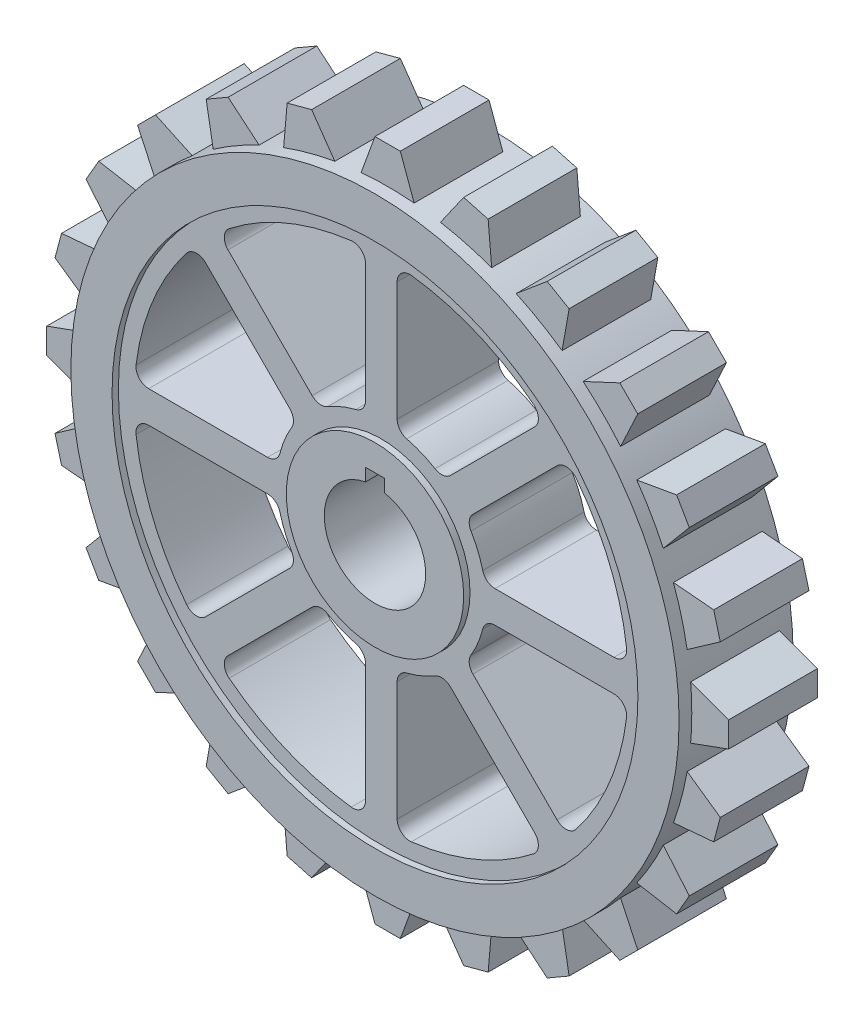
SolidWorks part; units mm, degrees
ref_plane "Front Plane" through (0, 0, 0) normal (0, 0, 1) x (1, 0, 0)
ref_plane "Top Plane" through (0, 0, 0) normal (0, 1, 0) x (1, 0, 0)
ref_plane "Right Plane" through (0, 0, 0) normal (1, 0, 0) x (0, 0, -1)
sketch "Sketch1" plane through (0, 0, 0) normal (0, 0, 1) x (1, 0, 0)
  line L0 (0, 54.6854) -> (0, -14) construction
  line L1 (54.7075, 0) -> (-72.8695, 0) construction
  line L2 (2.5, 36.7253) -> (2.5, 17.9444)
  line L3 (-2.5, 36.7253) -> (-2.5, 17.9444)
  line L4 (1.5, 9.8677) -> (1.5, 7.8581)
  line L5 (-1.5, 9.8677) -> (-1.5, 7.8581)
  line L6 (1.5, 9.8677) -> (-1.5, 9.8677)
  line L7 (24.201, 27.7365) -> (10.9208, 14.4563)
  line L8 (27.7365, 24.201) -> (14.4563, 10.9208)
  line L9 (36.7253, 2.5) -> (17.9444, 2.5)
  line L10 (36.7253, -2.5) -> (17.9444, -2.5)
  line L11 (27.7365, -24.201) -> (14.4563, -10.9208)
  line L12 (24.201, -27.7365) -> (10.9208, -14.4563)
  line L13 (2.5, -36.7253) -> (2.5, -17.9444)
  line L14 (-2.5, -36.7253) -> (-2.5, -17.9444)
  line L15 (-24.201, -27.7365) -> (-10.9208, -14.4563)
  line L16 (-27.7365, -24.201) -> (-14.4563, -10.9208)
  line L17 (-36.7253, -2.5) -> (-17.9444, -2.5)
  line L18 (-36.7253, 2.5) -> (-17.9444, 2.5)
  line L19 (-27.7365, 24.201) -> (-14.4563, 10.9208)
  line L20 (-24.201, 27.7365) -> (-10.9208, 14.4563)
  line L21 (-2, 53.8173) -> (2, 53.8173)
  line L22 (2, 53.8173) -> (4.1838, 47.8173)
  line L23 (-2, 53.8173) -> (-4.1838, 47.8173)
  line L24 (2, 53.8173) -> (4.1838, 47.8173)
  line L25 (-2, 53.8173) -> (-4.1838, 47.8173)
  line L26 (11.9971, 52.5012) -> (15.8608, 51.4659)
  line L27 (15.8608, 51.4659) -> (16.4173, 45.1051)
  line L28 (11.9971, 52.5012) -> (8.3348, 47.2708)
  line L29 (15.8608, 51.4659) -> (16.4173, 45.1051)
  line L30 (11.9971, 52.5012) -> (8.3348, 47.2708)
  line L31 (14.1536, 52.8221) -> (-3.6235, -13.523) construction
  line L32 (25.1766, 47.6072) -> (28.6407, 45.6072)
  line L33 (28.6407, 45.6072) -> (27.532, 39.3191)
  line L34 (25.1766, 47.6072) -> (20.2854, 43.5029)
  line L35 (28.6407, 45.6072) -> (27.532, 39.3191)
  line L36 (25.1766, 47.6072) -> (20.2854, 43.5029)
  line L37 (27.3427, 47.359) -> (-7, -12.1244) construction
  line L38 (36.6404, 39.4688) -> (39.4688, 36.6404)
  line L39 (39.4688, 36.6404) -> (36.7704, 30.8535)
  line L40 (36.6404, 39.4688) -> (30.8535, 36.7704)
  line L41 (39.4688, 36.6404) -> (36.7704, 30.8535)
  line L42 (36.6404, 39.4688) -> (30.8535, 36.7704)
  line L43 (38.6684, 38.6684) -> (-9.8995, -9.8995) construction
  line L44 (45.6072, 28.6407) -> (47.6072, 25.1766)
  line L45 (47.6072, 25.1766) -> (43.5029, 20.2854)
  line L46 (45.6072, 28.6407) -> (39.3191, 27.532)
  line L47 (47.6072, 25.1766) -> (43.5029, 20.2854)
  line L48 (45.6072, 28.6407) -> (39.3191, 27.532)
  line L49 (47.359, 27.3427) -> (-12.1244, -7) construction
  line L50 (51.4659, 15.8608) -> (52.5012, 11.9971)
  line L51 (52.5012, 11.9971) -> (47.2708, 8.3348)
  line L52 (51.4659, 15.8608) -> (45.1051, 16.4173)
  line L53 (52.5012, 11.9971) -> (47.2708, 8.3348)
  line L54 (51.4659, 15.8608) -> (45.1051, 16.4173)
  line L55 (52.8221, 14.1536) -> (-13.523, -3.6235) construction
  line L56 (53.8173, 2) -> (53.8173, -2)
  line L57 (53.8173, -2) -> (47.8173, -4.1838)
  line L58 (53.8173, 2) -> (47.8173, 4.1838)
  line L59 (53.8173, -2) -> (47.8173, -4.1838)
  line L60 (53.8173, 2) -> (47.8173, 4.1838)
  line L61 (54.6854, 0) -> (-14, 0) construction
  line L62 (52.5012, -11.9971) -> (51.4659, -15.8608)
  line L63 (51.4659, -15.8608) -> (45.1051, -16.4173)
  line L64 (52.5012, -11.9971) -> (47.2708, -8.3348)
  line L65 (51.4659, -15.8608) -> (45.1051, -16.4173)
  line L66 (52.5012, -11.9971) -> (47.2708, -8.3348)
  line L67 (52.8221, -14.1536) -> (-13.523, 3.6235) construction
  line L68 (47.6072, -25.1766) -> (45.6072, -28.6407)
  line L69 (45.6072, -28.6407) -> (39.3191, -27.532)
  line L70 (47.6072, -25.1766) -> (43.5029, -20.2854)
  line L71 (45.6072, -28.6407) -> (39.3191, -27.532)
  line L72 (47.6072, -25.1766) -> (43.5029, -20.2854)
  line L73 (47.359, -27.3427) -> (-12.1244, 7) construction
  line L74 (39.4688, -36.6404) -> (36.6404, -39.4688)
  line L75 (36.6404, -39.4688) -> (30.8535, -36.7704)
  line L76 (39.4688, -36.6404) -> (36.7704, -30.8535)
  line L77 (36.6404, -39.4688) -> (30.8535, -36.7704)
  line L78 (39.4688, -36.6404) -> (36.7704, -30.8535)
  line L79 (38.6684, -38.6684) -> (-9.8995, 9.8995) construction
  line L80 (28.6407, -45.6072) -> (25.1766, -47.6072)
  line L81 (25.1766, -47.6072) -> (20.2854, -43.5029)
  line L82 (28.6407, -45.6072) -> (27.532, -39.3191)
  line L83 (25.1766, -47.6072) -> (20.2854, -43.5029)
  line L84 (28.6407, -45.6072) -> (27.532, -39.3191)
  line L85 (27.3427, -47.359) -> (-7, 12.1244) construction
  line L86 (15.8608, -51.4659) -> (11.9971, -52.5012)
  line L87 (11.9971, -52.5012) -> (8.3348, -47.2708)
  line L88 (15.8608, -51.4659) -> (16.4173, -45.1051)
  line L89 (11.9971, -52.5012) -> (8.3348, -47.2708)
  line L90 (15.8608, -51.4659) -> (16.4173, -45.1051)
  line L91 (14.1536, -52.8221) -> (-3.6235, 13.523) construction
  line L92 (2, -53.8173) -> (-2, -53.8173)
  line L93 (-2, -53.8173) -> (-4.1838, -47.8173)
  line L94 (2, -53.8173) -> (4.1838, -47.8173)
  line L95 (-2, -53.8173) -> (-4.1838, -47.8173)
  line L96 (2, -53.8173) -> (4.1838, -47.8173)
  line L97 (0, -54.6854) -> (0, 14) construction
  line L98 (-11.9971, -52.5012) -> (-15.8608, -51.4659)
  line L99 (-15.8608, -51.4659) -> (-16.4173, -45.1051)
  line L100 (-11.9971, -52.5012) -> (-8.3348, -47.2708)
  line L101 (-15.8608, -51.4659) -> (-16.4173, -45.1051)
  line L102 (-11.9971, -52.5012) -> (-8.3348, -47.2708)
  line L103 (-14.1536, -52.8221) -> (3.6235, 13.523) construction
  line L104 (-25.1766, -47.6072) -> (-28.6407, -45.6072)
  line L105 (-28.6407, -45.6072) -> (-27.532, -39.3191)
  line L106 (-25.1766, -47.6072) -> (-20.2854, -43.5029)
  line L107 (-28.6407, -45.6072) -> (-27.532, -39.3191)
  line L108 (-25.1766, -47.6072) -> (-20.2854, -43.5029)
  line L109 (-27.3427, -47.359) -> (7, 12.1244) construction
  line L110 (-36.6404, -39.4688) -> (-39.4688, -36.6404)
  line L111 (-39.4688, -36.6404) -> (-36.7704, -30.8535)
  line L112 (-36.6404, -39.4688) -> (-30.8535, -36.7704)
  line L113 (-39.4688, -36.6404) -> (-36.7704, -30.8535)
  line L114 (-36.6404, -39.4688) -> (-30.8535, -36.7704)
  line L115 (-38.6684, -38.6684) -> (9.8995, 9.8995) construction
  line L116 (-45.6072, -28.6407) -> (-47.6072, -25.1766)
  line L117 (-47.6072, -25.1766) -> (-43.5029, -20.2854)
  line L118 (-45.6072, -28.6407) -> (-39.3191, -27.532)
  line L119 (-47.6072, -25.1766) -> (-43.5029, -20.2854)
  line L120 (-45.6072, -28.6407) -> (-39.3191, -27.532)
  line L121 (-47.359, -27.3427) -> (12.1244, 7) construction
  line L122 (-51.4659, -15.8608) -> (-52.5012, -11.9971)
  line L123 (-52.5012, -11.9971) -> (-47.2708, -8.3348)
  line L124 (-51.4659, -15.8608) -> (-45.1051, -16.4173)
  line L125 (-52.5012, -11.9971) -> (-47.2708, -8.3348)
  line L126 (-51.4659, -15.8608) -> (-45.1051, -16.4173)
  line L127 (-52.8221, -14.1536) -> (13.523, 3.6235) construction
  line L128 (-53.8173, -2) -> (-53.8173, 2)
  line L129 (-53.8173, 2) -> (-47.8173, 4.1838)
  line L130 (-53.8173, -2) -> (-47.8173, -4.1838)
  line L131 (-53.8173, 2) -> (-47.8173, 4.1838)
  line L132 (-53.8173, -2) -> (-47.8173, -4.1838)
  line L133 (-54.6854, 0) -> (14, 0) construction
  line L134 (-52.5012, 11.9971) -> (-51.4659, 15.8608)
  line L135 (-51.4659, 15.8608) -> (-45.1051, 16.4173)
  line L136 (-52.5012, 11.9971) -> (-47.2708, 8.3348)
  line L137 (-51.4659, 15.8608) -> (-45.1051, 16.4173)
  line L138 (-52.5012, 11.9971) -> (-47.2708, 8.3348)
  line L139 (-52.8221, 14.1536) -> (13.523, -3.6235) construction
  line L140 (-47.6072, 25.1766) -> (-45.6072, 28.6407)
  line L141 (-45.6072, 28.6407) -> (-39.3191, 27.532)
  line L142 (-47.6072, 25.1766) -> (-43.5029, 20.2854)
  line L143 (-45.6072, 28.6407) -> (-39.3191, 27.532)
  line L144 (-47.6072, 25.1766) -> (-43.5029, 20.2854)
  line L145 (-47.359, 27.3427) -> (12.1244, -7) construction
  line L146 (-39.4688, 36.6404) -> (-36.6404, 39.4688)
  line L147 (-36.6404, 39.4688) -> (-30.8535, 36.7704)
  line L148 (-39.4688, 36.6404) -> (-36.7704, 30.8535)
  line L149 (-36.6404, 39.4688) -> (-30.8535, 36.7704)
  line L150 (-39.4688, 36.6404) -> (-36.7704, 30.8535)
  line L151 (-38.6684, 38.6684) -> (9.8995, -9.8995) construction
  line L152 (-28.6407, 45.6072) -> (-25.1766, 47.6072)
  line L153 (-25.1766, 47.6072) -> (-20.2854, 43.5029)
  line L154 (-28.6407, 45.6072) -> (-27.532, 39.3191)
  line L155 (-25.1766, 47.6072) -> (-20.2854, 43.5029)
  line L156 (-28.6407, 45.6072) -> (-27.532, 39.3191)
  line L157 (-27.3427, 47.359) -> (7, -12.1244) construction
  line L158 (-15.8608, 51.4659) -> (-11.9971, 52.5012)
  line L159 (-11.9971, 52.5012) -> (-8.3348, 47.2708)
  line L160 (-15.8608, 51.4659) -> (-16.4173, 45.1051)
  line L161 (-11.9971, 52.5012) -> (-8.3348, 47.2708)
  line L162 (-15.8608, 51.4659) -> (-16.4173, 45.1051)
  line L163 (-14.1536, 52.8221) -> (3.6235, -13.523) construction
  arc A0 (-1.5, 7.8581) -> (1.5, 7.8581) centre (0, 0) ccw
  circle A1 centre (0, 0) radius 14
  arc A2 (-4.0135, 16.0044) -> (-8.4789, 14.1548) centre (0, 0) ccw
  arc A6 (-4.7432, 38.7105) -> (-24.0185, 30.7264) centre (0, 0) ccw
  circle A7 centre (0, 0) radius 41.5
  circle A8 centre (0, 0) radius 48
  arc A9 (8.4789, 14.1548) -> (4.0135, 16.0044) centre (0, 0) ccw
  arc A10 (24.0185, 30.7264) -> (4.7432, 38.7105) centre (0, 0) ccw
  arc A11 (38.7105, 4.7432) -> (30.7264, 24.0185) centre (0, 0) ccw
  arc A12 (16.0044, 4.0135) -> (14.1548, 8.4789) centre (0, 0) ccw
  arc A13 (-14.1548, 8.4789) -> (-16.0044, 4.0135) centre (0, 0) ccw
  arc A14 (-30.7264, 24.0185) -> (-38.7105, 4.7432) centre (0, 0) ccw
  arc A15 (14.1548, -8.4789) -> (16.0044, -4.0135) centre (0, 0) ccw
  arc A16 (30.7264, -24.0185) -> (38.7105, -4.7432) centre (0, 0) ccw
  arc A17 (4.7432, -38.7105) -> (24.0185, -30.7264) centre (0, 0) ccw
  arc A18 (4.0135, -16.0044) -> (8.4789, -14.1548) centre (0, 0) ccw
  arc A19 (-8.4789, -14.1548) -> (-4.0135, -16.0044) centre (0, 0) ccw
  arc A20 (-24.0185, -30.7264) -> (-4.7432, -38.7105) centre (0, 0) ccw
  arc A21 (-16.0044, -4.0135) -> (-14.1548, -8.4789) centre (0, 0) ccw
  arc A22 (-38.7105, -4.7432) -> (-30.7264, -24.0185) centre (0, 0) ccw
  arc A23 (36.7253, 2.5) -> (38.7105, 4.7432) centre (36.7253, 4.5) ccw
  arc A24 (27.7365, 24.201) -> (30.7264, 24.0185) centre (29.1507, 22.7868) cw
  arc A25 (14.4563, 10.9208) -> (14.1548, 8.4789) centre (15.8706, 9.5066) ccw
  arc A26 (17.9444, 2.5) -> (16.0044, 4.0135) centre (17.9444, 4.5) cw
  arc A27 (-36.7253, 2.5) -> (-38.7105, 4.7432) centre (-36.7253, 4.5) cw
  arc A28 (24.201, 27.7365) -> (24.0185, 30.7264) centre (22.7868, 29.1507) ccw
  arc A29 (2.5, 36.7253) -> (4.7432, 38.7105) centre (4.5, 36.7253) cw
  arc A30 (-27.7365, 24.201) -> (-30.7264, 24.0185) centre (-29.1507, 22.7868) ccw
  arc A31 (-24.201, 27.7365) -> (-24.0185, 30.7264) centre (-22.7868, 29.1507) cw
  arc A32 (-2.5, 36.7253) -> (-4.7432, 38.7105) centre (-4.5, 36.7253) ccw
  arc A33 (10.9208, 14.4563) -> (8.4789, 14.1548) centre (9.5066, 15.8706) cw
  arc A34 (-2.5, 17.9444) -> (-4.0135, 16.0044) centre (-4.5, 17.9444) cw
  arc A35 (-10.9208, 14.4563) -> (-8.4789, 14.1548) centre (-9.5066, 15.8706) ccw
  arc A36 (-14.4563, 10.9208) -> (-14.1548, 8.4789) centre (-15.8706, 9.5066) cw
  arc A37 (-17.9444, 2.5) -> (-16.0044, 4.0135) centre (-17.9444, 4.5) ccw
  arc A38 (-36.7253, -2.5) -> (-38.7105, -4.7432) centre (-36.7253, -4.5) ccw
  arc A39 (-27.7365, -24.201) -> (-30.7264, -24.0185) centre (-29.1507, -22.7868) cw
  arc A40 (-14.4563, -10.9208) -> (-14.1548, -8.4789) centre (-15.8706, -9.5066) ccw
  arc A41 (-17.9444, -2.5) -> (-16.0044, -4.0135) centre (-17.9444, -4.5) cw
  arc A42 (-24.201, -27.7365) -> (-24.0185, -30.7264) centre (-22.7868, -29.1507) ccw
  arc A43 (-10.9208, -14.4563) -> (-8.4789, -14.1548) centre (-9.5066, -15.8706) cw
  arc A44 (-2.5, -17.9444) -> (-4.0135, -16.0044) centre (-4.5, -17.9444) ccw
  arc A45 (-2.5, -36.7253) -> (-4.7432, -38.7105) centre (-4.5, -36.7253) cw
  arc A46 (2.5, -36.7253) -> (4.7432, -38.7105) centre (4.5, -36.7253) ccw
  arc A47 (24.201, -27.7365) -> (24.0185, -30.7264) centre (22.7868, -29.1507) cw
  arc A48 (2.5, -17.9444) -> (4.0135, -16.0044) centre (4.5, -17.9444) cw
  arc A49 (10.9208, -14.4563) -> (8.4789, -14.1548) centre (9.5066, -15.8706) ccw
  arc A50 (27.7365, -24.201) -> (30.7264, -24.0185) centre (29.1507, -22.7868) ccw
  arc A51 (36.7253, -2.5) -> (38.7105, -4.7432) centre (36.7253, -4.5) cw
  arc A52 (14.4563, -10.9208) -> (14.1548, -8.4789) centre (15.8706, -9.5066) cw
  arc A53 (17.9444, -2.5) -> (16.0044, -4.0135) centre (17.9444, -4.5) ccw
  arc A54 (2.5, 17.9444) -> (4.0135, 16.0044) centre (4.5, 17.9444) ccw
  point P47 (0, 0)
  point P254 (0, 0)
  dimension "D1" = 16
  dimension "D2" = 28
  dimension "D3" = 33
  dimension "D4" = 96
  dimension "D5" = 83
  dimension "D6" = 78
  dimension "D10" = 2
  dimension "D11" = 2
  dimension "D12" = 2
  dimension "D7" = 5
  dimension "D8" = 3
  dimension "D13" = 4
  dimension "D14" = 40
  dimension "D15" = 6
  dimension "D9" = 8
  dimension "D16" = 24
extrude "Boss-Extrude1" add sketch "Sketch1" along normal blind 16 and the other way blind 2 contours A1 A0 L5 L6 L4 | A8 A7 region at (0, 46.6424, 0) region at (-13.604, 0, 0)
extrude "Boss-Extrude2" add sketch "Sketch1<3>" along normal blind 15 and the other way blind 1 contours A7 A54 L2 A29 A10 A28 L7 A33 A9 A53 L10 A51 A16 A50 L11 A52 A15 A49 L12 A47 A17 A46 L13 A48 A18 A37 L18 A27 A14 A30 L19 A36 A13 A35 L20 A31 A6 A32 L3 A34 A2 A1 L9 A26 region at (-40.3262, 0, 0)
sketch "Sketch1<3>" plane through (0, 0, 0) normal (0, 0, 1) x (1, 0, 0) same geometry as "Sketch1"
extrude "Boss-Extrude3" add sketch "Sketch1<4>" along normal blind 14 contours A8 L51 L50 L52 | A8 L45 L44 L46 | A8 L39 L38 L40 | A8 L33 L32 L34 | A8 L27 L26 L28 | A8 L22 L21 L23 | A8 L159 L158 L160 | A8 L153 L152 L154 | A8 L147 L146 L148 | A8 L141 L140 L142 | A8 L135 L134 L136 | A8 L57 L56 L58 | A8 L63 L62 L64 | A8 L69 L68 L70 | A8 L75 L74 L76 | A8 L81 L80 L82 | A8 L87 L86 L88 | A8 L93 L92 L94 | A8 L99 L98 L100 | A8 L105 L104 L106 | A8 L111 L110 L112 | A8 L117 L116 L118 | A8 L123 L122 L124 | A8 L129 L128 L130 region at (0, 50.5369, 0) region at (-13.0799, 48.8149, 0) region at (13.0799, 48.8149, 0) region at (-25.2684, 43.7662, 0) region at (25.2684, 43.7662, 0) region at (-35.735, 35.735, 0) region at (35.735, 35.735, 0) region at (-43.7662, 25.2684, 0) region at (43.7662, 25.2684, 0) region at (-48.8149, 13.0799, 0) region at (48.8149, 13.0799, 0) region at (-50.5369, 0, 0) region at (50.5369, 0, 0) region at (-48.8149, -13.0799, 0) region at (48.8149, -13.0799, 0) region at (-43.7662, -25.2684, 0) region at (43.7662, -25.2684, 0) region at (-35.735, -35.735, 0) region at (35.735, -35.735, 0) region at (-25.2684, -43.7662, 0) region at (25.2684, -43.7662, 0) region at (-13.0799, -48.8149, 0) region at (13.0799, -48.8149, 0) region at (0, -50.5369, 0)
sketch "Sketch1<4>" plane through (0, 0, 0) normal (0, 0, 1) x (1, 0, 0) same geometry as "Sketch1"
